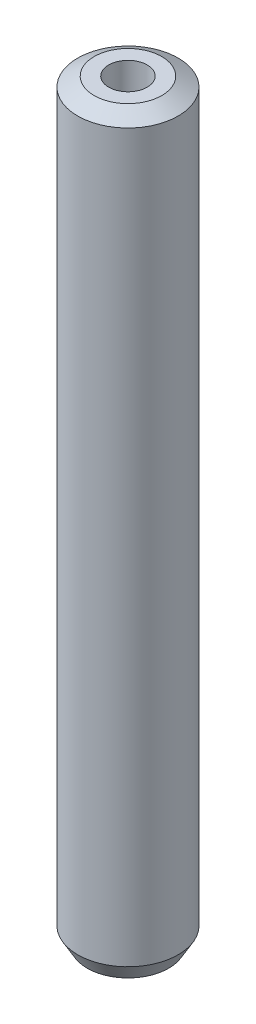
SolidWorks part; units mm, degrees
ref_plane "Front Plane" through (0, 0, 0) normal (0, 0, 1) x (1, 0, 0)
ref_plane "Top Plane" through (0, 0, 0) normal (0, 1, 0) x (1, 0, 0)
ref_plane "Right Plane" through (0, 0, 0) normal (1, 0, 0) x (0, 0, -1)
sketch "Sketch1" plane through (0, 0, 0) normal (0, 1, 0) x (1, 0, 0)
  circle A0 centre (0, 0) radius 5
  dimension "SHAFT_OD" = 10
extrude "Boss-Extrude1" add sketch "Sketch1" along normal blind 74.864
sketch "Sketch2" plane through (0, 0, 0) normal (0, 1, 0) x (1, 0, 0)
  circle A0 centre (0, 0) radius 1.9187
  dimension "BORE_D" = 3.8373
extrude "Cut-Extrude1" cut sketch "Sketch2" along normal through all
chamfer "Chamfer1" distance 0.9447 angle 60 2 edges at (0, 74.864, 5) (0, 0, 5) first distance on face at (0, 74.864, 5) first distance on face at (0, 0, 1.9187)
